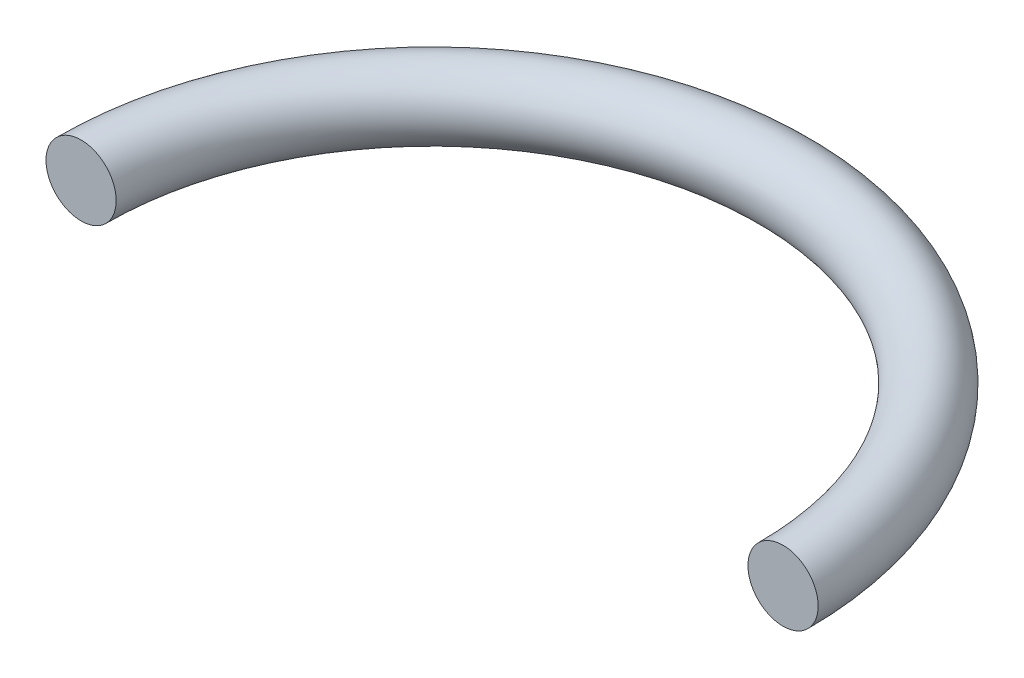
SolidWorks part; units mm, degrees
ref_plane "Front Plane" through (0, 0, 0) normal (0, 0, 1) x (1, 0, 0)
ref_plane "Top Plane" through (0, 0, 0) normal (0, 1, 0) x (1, 0, 0)
ref_plane "Right Plane" through (0, 0, 0) normal (1, 0, 0) x (0, 0, -1)
sketch "Sketch1" plane through (0, 0, 0) normal (0, 0, 1) x (1, 0, 0)
  line L0 (0, 0) -> (0, -30.8327) construction
  circle A0 centre (50, 0) radius 5
  dimension "D1" = 10
  dimension "D2" = 50
revolve "Revolve1" add sketch "Sketch1" angle 180 about L0 reverse direction yes
ref_point "Point1"
ref_point "Point2"
ref_axis "Axis1" through (-50, 0, 0) along (0, 0, 1)
ref_axis "Axis2" through (50, 0, 0) along (0, 0, 1)
